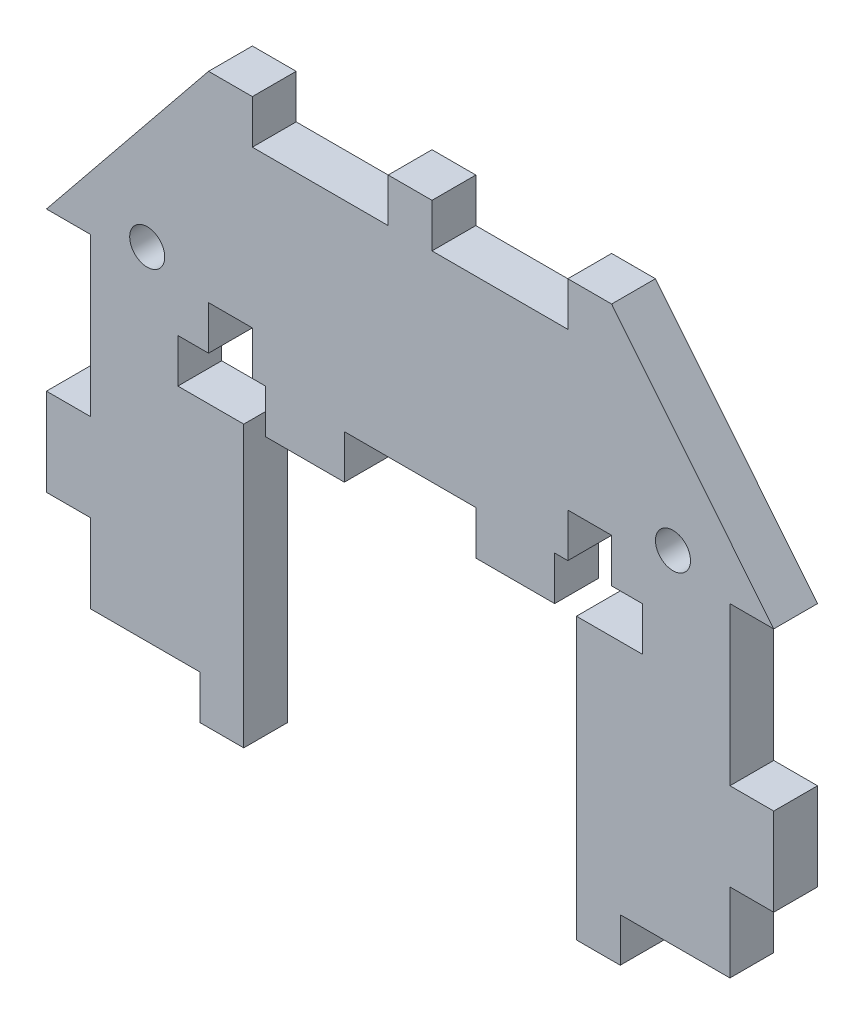
SolidWorks part; units mm, degrees
ref_plane "Plan de face" through (0, 0, 0) normal (0, 0, 1) x (1, 0, 0)
ref_plane "Plan de dessus" through (0, 0, 0) normal (0, 1, 0) x (1, 0, 0)
ref_plane "Plan de droite" through (0, 0, 0) normal (1, 0, 0) x (0, 0, -1)
sketch "Esquisse1" plane through (0, 0, 0) normal (0, 0, 1) x (1, 0, 0)
  line L0 (-23, 0) -> (-41.5, -22.86)
  line L1 (-41.5, -22.86) -> (-41.5, -64.86)
  line L2 (-41.5, -64.86) -> (-18.9833, -64.86)
  line L3 (0, -46.21) -> (0, 0) construction
  line L4 (18.9833, -64.86) -> (18.9833, -32.86)
  line L5 (41.5, -64.86) -> (18.9833, -64.86)
  line L6 (41.5, -22.86) -> (41.5, -64.86)
  line L7 (-23, 0) -> (23, 0)
  line L8 (-18.9833, -32.86) -> (18.9833, -32.86)
  line L9 (-18.9833, -64.86) -> (-18.9833, -32.86)
  line L10 (23, 0) -> (41.5, -22.86)
  dimension "D1" = 46
  dimension "D2" = 22.86
  dimension "D3" = 83
  dimension "D4" = 42
  dimension "D5" = 32
extrude "Boss.-Extru.1" add sketch "Esquisse1" along normal blind 5
sketch "Esquisse2" plane through (0, 0, 5) normal (0, 0, 1) x (1, 0, 0)
  line L0 (41.5, -64.86) -> (41.5, -22.86) construction
  line L1 (36.5, -22.86) -> (41.5, -22.86)
  line L2 (36.5, -22.86) -> (36.5, -40.86)
  line L3 (36.5, -40.86) -> (41.5, -40.86)
  line L4 (41.5, -22.86) -> (41.5, -40.86)
  line L5 (18.9833, -64.86) -> (41.5, -64.86) construction
  line L6 (23.9833, -64.86) -> (41.5, -64.86)
  line L7 (36.5, -50.86) -> (36.5, -59.86)
  line L8 (36.5, -50.86) -> (41.5, -50.86)
  line L9 (41.5, -64.86) -> (41.5, -50.86)
  line L10 (-18, -5) -> (-18, 0) construction
  line L11 (0, 0) -> (0, -59.86) construction
  line L12 (23, 0) -> (-23, 0) construction
  line L13 (-41.5, -64.86) -> (-41.5, -50.86)
  line L14 (-36.5, -50.86) -> (-41.5, -50.86)
  line L15 (-23.9833, -64.86) -> (-41.5, -64.86)
  line L16 (-23.9833, -59.86) -> (-23.9833, -64.86)
  line L17 (-41.5, -22.86) -> (-41.5, -40.86)
  line L18 (-36.5, -40.86) -> (-41.5, -40.86)
  line L19 (-36.5, -22.86) -> (-36.5, -40.86)
  line L20 (-36.5, -22.86) -> (-41.5, -22.86)
  line L21 (36.5, -59.86) -> (23.9833, -59.86)
  line L22 (23.9833, -59.86) -> (23.9833, -64.86)
  line L23 (18.9833, -64.86) -> (41.5, -64.86) construction
  line L24 (23.9833, -59.86) -> (23.9833, -64.86) construction
  line L25 (-36.5, -50.86) -> (-36.5, -59.86)
  line L26 (-36.5, -59.86) -> (-23.9833, -59.86)
  line L27 (-18.9833, -32.86) -> (18.9833, -32.86) construction
  line L28 (-26.5, -27.86) -> (-16.5, -27.86)
  line L29 (-26.5, -27.86) -> (-26.5, -32.86)
  line L30 (-26.5, -32.86) -> (-16.5, -32.86)
  line L31 (-16.5, -27.86) -> (-16.5, -32.86)
  line L32 (-7.5, -27.86) -> (-7.5, -32.86)
  line L33 (-18, 0) -> (-2.5, 0)
  line L34 (7.5, -27.86) -> (7.5, -32.86)
  line L35 (16.5, -27.86) -> (16.5, -32.86)
  line L36 (26.5, -32.86) -> (16.5, -32.86)
  line L37 (26.5, -27.86) -> (26.5, -32.86)
  line L38 (26.5, -27.86) -> (16.5, -27.86)
  line L39 (-7.5, -27.86) -> (7.5, -27.86)
  line L40 (7.5, -32.86) -> (-7.5, -32.86)
  line L41 (-18, 0) -> (-18, -5)
  line L42 (-18, -5) -> (-2.5, -5)
  line L43 (-2.5, 0) -> (-2.5, -5)
  line L44 (2.5, 0) -> (2.5, -5)
  line L45 (18, -5) -> (2.5, -5)
  line L46 (18, 0) -> (18, -5)
  line L47 (18, 0) -> (2.5, 0)
  dimension "D1" = 10
  dimension "D2" = 14
  dimension "D3" = 5
  dimension "D4" = 10
extrude "Enlèv. mat.-Extru.1" cut sketch "Esquisse2" against normal blind 5
sketch "Esquisse3" plane through (0, 0, 5) normal (0, 0, 1) x (1, 0, 0)
  line L0 (26.5, -27.86) -> (16.5, -27.86) construction
  line L1 (18, -22.86) -> (23, -22.86)
  line L2 (18, -22.86) -> (18, -27.86)
  line L3 (18, -27.86) -> (23, -27.86)
  line L4 (23, -22.86) -> (23, -27.86)
  line L5 (23, -22.86) -> (23, -27.86) construction
  line L6 (0, 0) -> (0, -27.86) construction
  line L7 (7.5, -27.86) -> (-7.5, -27.86) construction
  line L8 (-23, -22.86) -> (-23, -27.86)
  line L9 (-18, -27.86) -> (-23, -27.86)
  line L10 (-18, -22.86) -> (-18, -27.86)
  line L11 (-18, -22.86) -> (-23, -22.86)
extrude "Enlèv. mat.-Extru.2" cut sketch "Esquisse3" against normal blind 5
hole_wizard "Trous de centrage Ø4.0mm1" positions "Esquisse4" profile "Esquisse5" hole size "Ø4.0" standard "Ansi Metric" end condition through all
sketch "Esquisse4" plane through (42.8876, 88.2204, -73) normal (0, 0, -1) x (0.8607, -0.5092, 0)
  point P0 (64.7609, -88.7167)
  point P3 (117.0387, -59.2713)
  point P6 (-109.8498, -71.7228)
  point P9 (-109.2114, -11.7262)
  point P12 (-7.1889, 130.9941)
  point P15 (44.4505, 100.4429)
sketch "Esquisse5" plane through (143.7978, 131.5996, -73) normal (1, 0, 0) x (0, 1, 0)
  line L0 (0, 0) -> (0, 78)
  line L1 (0, 78) -> (2, 78)
  line L2 (2, 78) -> (2, 0)
  line L3 (2, 0) -> (0, 0)
  line L4 (0, -6.35) -> (0, 107.95) construction
  dimension "Diamètre du perçage jusqu'au prochain" = 4
  dimension "Profondeur du perçage jusqu'au prochain" = 78
hole_wizard "Trous de centrage Ø4.0mm2" positions "Esquisse6" profile "Esquisse7" hole size "Ø4.0" standard "Ansi Metric" end condition through all
sketch "Esquisse6" plane through (42.8876, 88.2204, -73) normal (0, 0, -1) x (0.0106, 0.9999, 0)
  point P0 (64.7609, -88.7167)
  point P3 (117.0387, -59.2713)
  point P6 (-109.8498, -71.7228)
  point P9 (-109.2114, -11.7262)
  point P12 (-7.1889, 130.9941)
  point P15 (44.4505, 100.4429)
sketch "Esquisse7" plane through (-45.135, 153.9216, -73) normal (1, 0, 0) x (0, 1, 0)
  line L0 (0, 0) -> (0, 78)
  line L1 (0, 78) -> (2, 78)
  line L2 (2, 78) -> (2, 0)
  line L3 (2, 0) -> (0, 0)
  line L4 (0, -6.35) -> (0, 107.95) construction
  dimension "Diamètre du perçage jusqu'au prochain" = 4
  dimension "Profondeur du perçage jusqu'au prochain" = 78
hole_wizard "Trous de centrage Ø4.0mm3" positions "Esquisse8" profile "Esquisse9" hole size "Ø4.0" standard "Ansi Metric" end condition through all
sketch "Esquisse8" plane through (42.8876, 88.2204, -73) normal (0, 0, -1) x (-0.8713, -0.4908, 0)
  point P0 (64.7609, -88.7167)
  point P3 (117.0387, -59.2713)
  point P6 (-109.8498, -71.7228)
  point P9 (-109.2114, -11.7262)
  point P12 (-7.1889, 130.9941)
  point P15 (44.4505, 100.4429)
sketch "Esquisse9" plane through (30, -20.86, -73) normal (1, 0, 0) x (0, 1, 0)
  line L0 (0, 0) -> (0, 78)
  line L1 (0, 78) -> (2, 78)
  line L2 (2, 78) -> (2, 0)
  line L3 (2, 0) -> (0, 0)
  line L4 (0, -6.35) -> (0, 107.95) construction
  dimension "Diamètre du perçage jusqu'au prochain" = 4
  dimension "Profondeur du perçage jusqu'au prochain" = 78
